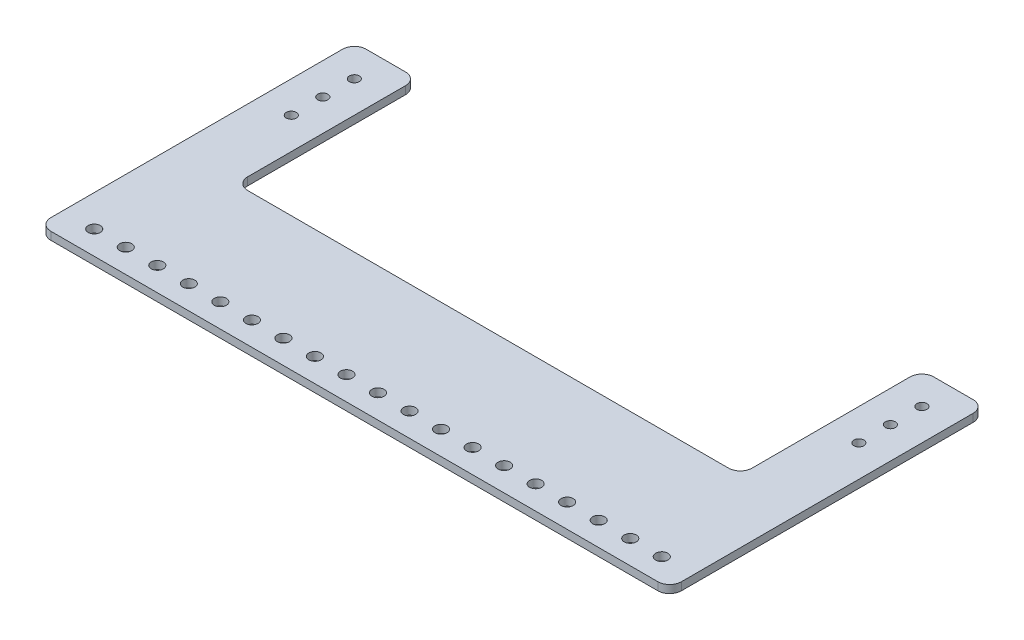
SolidWorks part; units mm, degrees
ref_plane "Front Plane" through (0, 0, 0) normal (0, 0, 1) x (1, 0, 0)
ref_plane "Top Plane" through (0, 0, 0) normal (0, 1, 0) x (1, 0, 0)
ref_plane "Right Plane" through (0, 0, 0) normal (1, 0, 0) x (0, 0, -1)
sketch "Sketch2" plane through (0, 0, 0) normal (0, 1, 0) x (1, 0, 0)
  line L0 (0, 63.5) -> (0, -63.5) construction
  line L1 (-127, -63.5) -> (127, -63.5)
  line L2 (-127, -63.5) -> (-127, 63.5)
  line L3 (-127, 63.5) -> (127, 63.5)
  line L4 (127, -63.5) -> (127, 63.5)
  line L5 (-127, -63.5) -> (127, 63.5) construction
  line L6 (-127, 63.5) -> (127, -63.5) construction
  line L7 (-101.6, 63.5) -> (101.6, 63.5)
  line L8 (-101.6, 63.5) -> (-101.6, -9.652)
  line L9 (-101.6, -9.652) -> (101.6, -9.652)
  line L10 (101.6, 63.5) -> (101.6, -9.652)
  line L11 (127, 63.5) -> (101.6, 63.5) construction
  line L12 (127, 63.5) -> (127, -9.652) construction
  line L13 (127, -9.652) -> (101.6, -9.652) construction
  line L14 (101.6, 63.5) -> (101.6, -9.652) construction
  circle A0 centre (-114.3, 50.8) radius 2.0193
  circle A1 centre (-114.3, 38.1) radius 2.0193
  circle A2 centre (-114.3, 25.4) radius 2.0193
  circle A6 centre (114.3, 25.4) radius 2.0193
  circle A7 centre (114.3, 38.1) radius 2.0193
  circle A8 centre (114.3, 50.8) radius 2.0193
  point P0 (0, 0)
  point P10 (0, -9.652)
  point P11 (0, -63.5)
  dimension "D8" = 4.0386
  dimension "D1" = 254
  dimension "D2" = 127
  dimension "D3" = 203.2
  dimension "D4" = 53.848
  dimension "D5" = 12.7
  dimension "D6" = 12.7
  dimension "D7" = 12.7
  dimension "D9" = 12.7
extrude "Boss-Extrude1" add sketch "Sketch2" along normal blind 3.175 contours L3 L10 L9 L8 L2 L1 L4 A7 A0 A1 A2 A6 A8 region at (0, 0, 23.2805)
fillet "Fillet1" radius 4.7625 8 edges at (127, 1.5875, -63.5) (-127, 1.5875, 63.5) (-127, 1.5875, -63.5) (-101.6, 1.5875, -63.5) (-101.6, 1.5875, 9.652) (101.6, 1.5875, 9.652) (101.6, 1.5875, -63.5) (127, 1.5875, 63.5)
sketch "Sketch3" plane through (0, 3.175, 0) normal (0, 1, 0) x (1, 0, 0)
  line L0 (-127, -58.7375) -> (-127, 58.7375) construction
  line L1 (-122.2375, -63.5) -> (122.2375, -63.5) construction
  line L2 (0, -9.652) -> (0, -63.5) construction
  line L3 (-96.8375, -9.652) -> (96.8375, -9.652) construction
  line L4 (127, -58.7375) -> (127, 58.7375) construction
  circle A0 centre (-114.3, -53.975) radius 2.4384
  circle A1 centre (-101.6, -53.975) radius 2.4384
  circle A2 centre (-88.9, -53.975) radius 2.4384
  circle A3 centre (-76.2, -53.975) radius 2.4384
  circle A4 centre (-63.5, -53.975) radius 2.4384
  circle A5 centre (-50.8, -53.975) radius 2.4384
  circle A6 centre (-38.1, -53.975) radius 2.4384
  circle A7 centre (-25.4, -53.975) radius 2.4384
  circle A8 centre (-12.7, -53.975) radius 2.4384
  circle A9 centre (0, -53.975) radius 2.4384
  circle A10 centre (12.7, -53.975) radius 2.4384
  circle A11 centre (25.4, -53.975) radius 2.4384
  circle A12 centre (38.1, -53.975) radius 2.4384
  circle A13 centre (50.8, -53.975) radius 2.4384
  circle A14 centre (63.5, -53.975) radius 2.4384
  circle A15 centre (76.2, -53.975) radius 2.4384
  circle A16 centre (88.9, -53.975) radius 2.4384
  circle A17 centre (101.6, -53.975) radius 2.4384
  circle A18 centre (114.3, -53.975) radius 2.4384
  dimension "D1" = 4.8768
  dimension "D2" = 12.7
  dimension "D3" = 9.525
  dimension "D4" = 12.7
  dimension "D5" = 12.7
  dimension "D7" = 12.7
  dimension "D6" = 17
extrude "Cut-Extrude1" cut sketch "Sketch3" against normal through all
